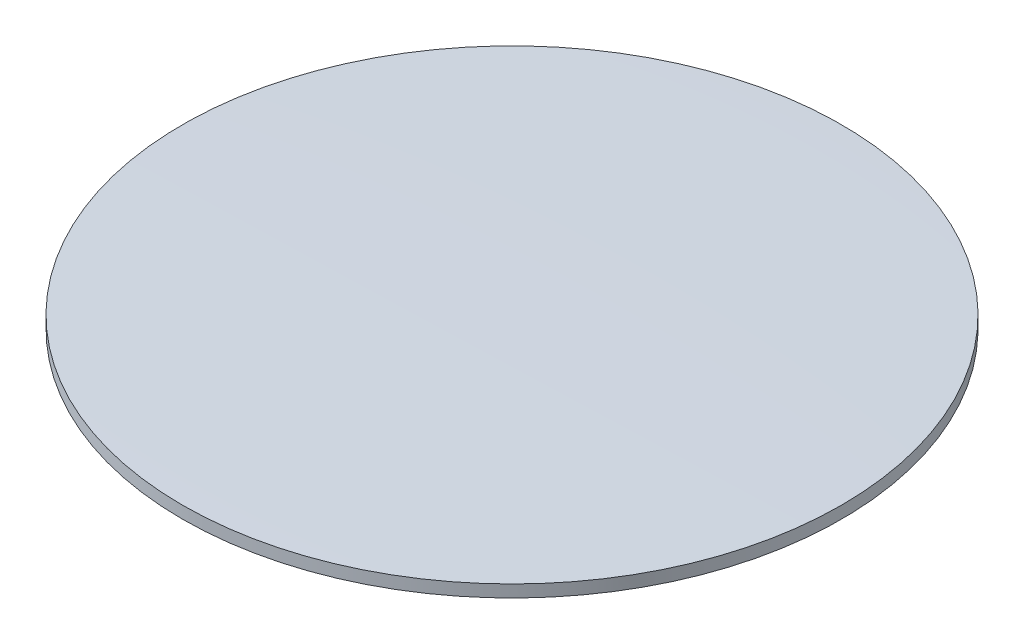
SolidWorks part; units mm, degrees
material "Verre"
ref_plane "Plan de face" through (0, 0, 0) normal (0, 0, 1) x (1, 0, 0)
ref_plane "Plan de dessus" through (0, 0, 0) normal (0, 1, 0) x (1, 0, 0)
ref_plane "Plan de droite" through (0, 0, 0) normal (1, 0, 0) x (0, 0, -1)
sketch "Esquisse1" plane through (0, 0, 0) normal (0, 0, 1) x (1, 0, 0)
  line L0 (0, 0) -> (20.1, 0)
  line L1 (20.1, 0) -> (20.1, 0.7424)
  line L2 (0, 1) -> (0, 0) construction
  line L3 (0, 0) -> (0, 1)
  ellipse E0 centre (0, 0) end of major axis (30, 0) minor radius 1 (20.1, 0.7424) -> (0, 1) ccw
  dimension "D1" = 20.1
  dimension "D2" = 30
  dimension "D3" = 1
revolve "Révolution1" add sketch "Esquisse1" angle 360 about L2
